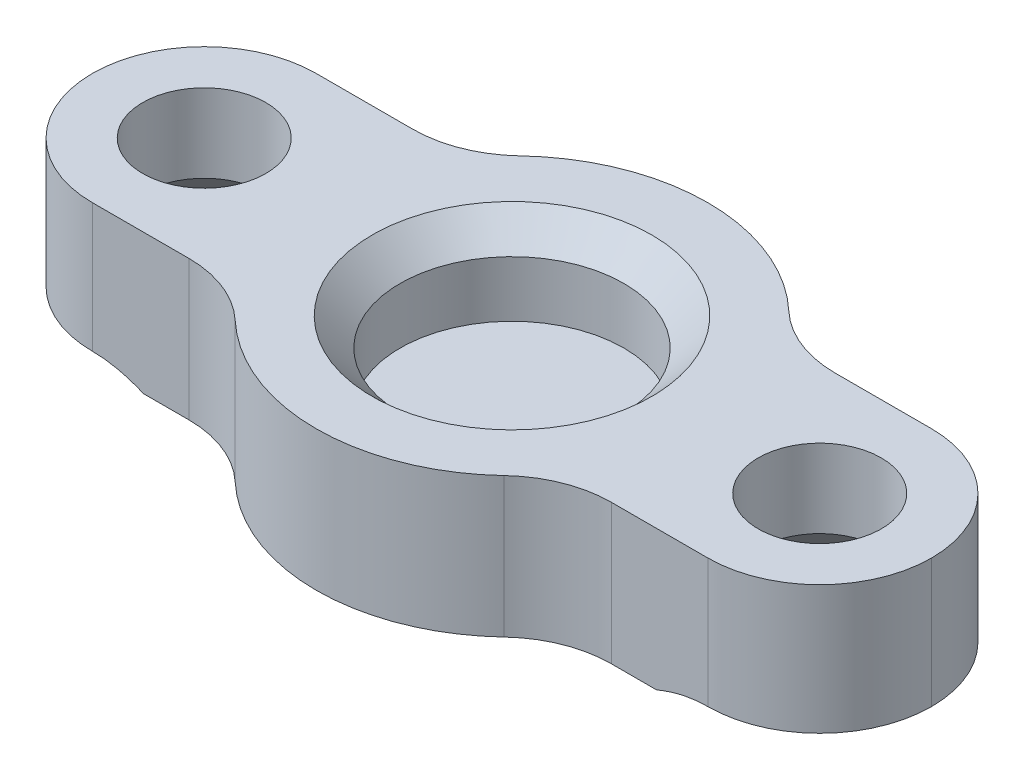
SolidWorks part; units mm, degrees
ref_plane "Front Plane" through (0, 0, 0) normal (0, 0, 1) x (1, 0, 0)
ref_plane "Top Plane" through (0, 0, 0) normal (0, 1, 0) x (1, 0, 0)
ref_plane "Right Plane" through (0, 0, 0) normal (1, 0, 0) x (0, 0, -1)
sketch "Sketch1" plane through (0, 0, 0) normal (0, 0, 1) x (1, 0, 0)
  line L0 (0, 0) -> (0, 7.0462) construction
  line L1 (0, 0) -> (-3.5, 0)
  line L2 (-3.5, 0) -> (-3.5, 2.5)
  line L3 (-3.5, 2.5) -> (-2, 2.5)
  line L4 (-2, 2.5) -> (-2, 1)
  line L5 (-2, 1) -> (0, 1)
  line L6 (0, 0) -> (0, 1)
  dimension "D1" = 2
  dimension "D2" = 1.5
  dimension "D3" = 1
  dimension "D4" = 1.5
revolve "Revolve1" add sketch "Sketch1" angle 360 about L0
chamfer "Chamfer2" distance 0.5 angle 45 1 edges at (0, 2.5, -2)
sketch "Sketch2" plane through (0, 2.5, 0) normal (0, 1, 0) x (1, 0, 0)
  line L0 (-2.8723, -2) -> (-7.5, -2)
  line L1 (-7.5, -2) -> (-7.5, 2)
  line L2 (-7.5, 2) -> (-2.8723, 2)
  line L3 (-7.5, 0) -> (-3.5, 0) construction
  line L4 (-2.8723, -2) -> (-2.8723, 2)
  circle A0 centre (0, 0) radius 3.5 construction
  point P2 (-7.5, 0)
  dimension "D1" = 4
extrude "Boss-Extrude1" add sketch "Sketch2" against normal up to surface (2.5 mm away) up to face at (0, 0, -3.5)
fillet "Fillet1" radius 2 4 edges at (-2.8723, 1.25, 2) (-2.8723, 1.25, -2) (-7.5, 1.25, -2) (-7.5, 1.25, 2)
hole_wizard "CSK for M2 Flat Head Machine Screw1" positions "Sketch3" profile "Sketch4" countersink size "M2" standard "ANSI Metric"
sketch "Sketch3" plane through (0, 0, 0) normal (0, -1, 0) x (-1, 0, 0)
  arc A1 (7.5, 0) -> (5.5, 2) centre (5.5, 0) ccw construction
  point P0 (5.5, 0)
sketch "Sketch4" plane through (-5.5, 0, 0) normal (1, 0, 0) x (0, 0, -1)
  line L0 (0, 0) -> (0, 5.8609)
  line L1 (0, 5.8609) -> (1.1, 5.2)
  line L2 (1.1, 5.2) -> (1.1, 1.1)
  line L3 (1.1, 1.1) -> (2.2, 0)
  line L5 (2.2, 0) -> (0, 0)
  line L6 (-1.1, 1.1) -> (-2.2, 0) construction
  line L10 (0, 5.8609) -> (-1.1, 5.2) construction
  line L11 (0, -6.35) -> (0, 107.95) construction
  dimension "Hole Dia." = 2.2
  dimension "Hole Depth" = 5.2
  dimension "Near C'Sink Dia." = 4.4
  dimension "Near C'Sink Angle" = 90
  dimension "Drill Angle" = 118
pattern_circular "CirPattern1" count 2 over 360 about axis through (0, 0, 0) along (0, -1, 0) of "CSK for M2 Flat Head Machine Screw1", "Boss-Extrude1", "Fillet1"
